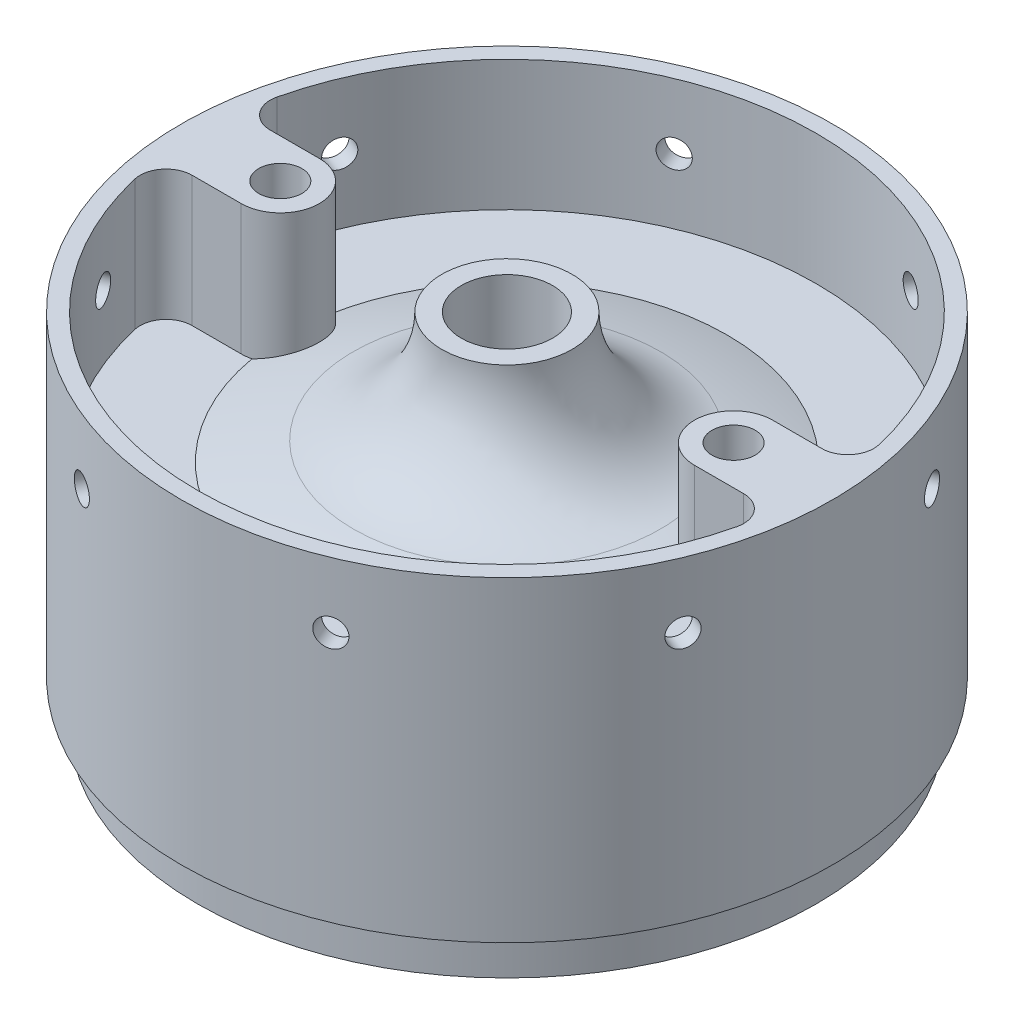
SolidWorks part; units mm, degrees
material "6061-T6 (SS)"
ref_plane "Front Plane" through (0, 0, 0) normal (0, 0, 1) x (1, 0, 0)
ref_plane "Top Plane" through (0, 0, 0) normal (0, 1, 0) x (1, 0, 0)
ref_plane "Right Plane" through (0, 0, 0) normal (1, 0, 0) x (0, 0, -1)
ref_axis "Axis1" through (0, 127.061, 0) along (0, -1, 0)
sketch "Sketch1" plane through (0, 0, 0) normal (0, 0, 1) x (1, 0, 0)
  line L0 (-63.5, 8.1831) -> (-63.5, 69.85)
  line L1 (-60.325, 6.35) -> (-63.5, 8.1831)
  line L2 (0, 127.061) -> (0, -81.9141) construction
  line L3 (-8.9065, 69.85) -> (-12.7, 69.85)
  line L4 (-60.325, 6.35) -> (-60.325, 0)
  line L5 (-60.325, 0) -> (-57.9438, 0)
  line L6 (55, 0) -> (-55, 0) construction
  line L7 (-60.325, 69.85) -> (-63.5, 69.85)
  line L8 (-63.5, 8.1831) -> (-60.325, 6.35)
  line L9 (-60.325, 44.45) -> (-42.968, 44.45)
  line L10 (-8.9065, 69.85) -> (-8.9065, 54.61)
  line L11 (-60.325, 44.45) -> (-60.325, 69.85)
  line L15 (-57.9438, 0) -> (-57.9438, 6.35)
  line L16 (-57.9438, 6.35) -> (-55.5728, 19.7961)
  arc A0 (-55.5728, 19.7961) -> (-42.968, 37.7227) centre (-36.5228, 19.7961) cw
  arc A1 (-42.968, 37.7227) -> (-19.868, 43.6485) centre (0, -81.7878) cw
  arc A2 (-29.9638, 48.1522) -> (-12.7, 69.85) centre (-34.9672, 69.85) ccw
  arc A3 (-42.968, 44.45) -> (-29.9638, 48.1522) centre (0, -81.7878) cw
  arc A4 (-8.9065, 54.61) -> (-19.868, 43.6485) centre (-19.868, 54.61) cw
  point P14 (-59.1344, 0)
  dimension "D5" = 19.05
  dimension "D6" = 127
  dimension "D7" = 133.35
  dimension "D8" = 63.5
  dimension "D12" = 3.175
  dimension "D14" = 15.24
  dimension "D2" = 170
  dimension "D3" = 6.35
  dimension "D4" = 2.3813
  dimension "D9" = 25.4
  dimension "D10" = 3.175
  dimension "D11" = 12.7
  dimension "D13" = 8.9065
  dimension "D16" = 63.5
  dimension "D17" = 120
revolve "Revolve2" add sketch "Sketch1" angle 360 about axis through (0, 127.061, 0) along (0, -1, 0) region at (-43.3861, 40.2185, 0)
sketch "Sketch2" plane through (0, 0, 0) normal (0, 0, 1) x (1, 0, 0)
  line L0 (0, 127.061) -> (0, -81.9141) construction
  line L1 (0, 87.1374) -> (-97.8719, 87.1374)
  line L2 (0, 87.1374) -> (0, -26.2798)
  line L3 (0, -26.2798) -> (-97.8719, -26.2798)
  line L4 (-97.8719, 87.1374) -> (-97.8719, -26.2798)
revolve "Cut-Revolve1" [suppressed] cut sketch "Sketch2" angle 315 about axis through (0, 127.061, 0) along (0, -1, 0)
ref_plane "Plane1" through (0, 57.15, 0) normal (0, 1, 0) x (1, 0, 0)
ref_plane "Plane2" through (0, 0, 0) normal (0.9239, 0, 0.3827) x (0, -1, 0)
ref_axis "Axis2" through (83.9699, 57.15, -202.7212) along (-0.3827, 0, 0.9239)
hole_wizard "#3 (0.213) Diameter Hole1" positions "3DSketch3" profile "Sketch5" hole size "#3" standard "ANSI Inch"
sketch3d "3DSketch3"
  line L0 (83.9699, 57.15, -202.7212) -> (-38.5912, 57.15, 93.1674) construction
  point P0 (-24.3004, 57.15, 58.6664)
sketch "Sketch5" plane through (-24.3004, 57.15, 58.6664) normal (0, 1, 0) x (0.9239, 0, 0.3827)
  line L0 (0, 0) -> (0, 13.3094)
  line L1 (0, 13.3094) -> (2.7051, 11.684)
  line L2 (2.7051, 11.684) -> (2.7051, 0)
  line L5 (2.7051, 0) -> (0, 0)
  line L10 (0, 13.3094) -> (-2.7051, 11.684) construction
  line L11 (0, -6.35) -> (0, 107.95) construction
  dimension "Hole Dia." = 5.4102
  dimension "Hole Depth" = 11.684
  dimension "Drill Angle" = 118
pattern_circular "CirPattern1" count 8 over 360 about axis through (0, 127.061, 0) along (0, -1, 0) of "#3 (0.213) Diameter Hole1"
cosmetic thread "Cosmetic Thread1" parameters "D2"=6.35
hole_wizard "Q (0.332) Diameter Hole2" positions "Sketch9" profile "Sketch10" hole size "Q" standard "ANSI Inch" end condition through all
sketch "Sketch9" plane through (0, 44.45, 0) normal (0, 1, 0) x (1, 0, 0)
  line L0 (-55, 0) -> (55, 0) construction
  circle A1 centre (0, 0) radius 42.968 construction
  point P0 (-44.196, 0)
  dimension "D1" = 44.196
sketch "Sketch10" plane through (-44.196, 44.45, 0) normal (1, 0, 0) x (0, 0, 1)
  line L0 (0, 0) -> (0, 44.45)
  line L1 (0, 44.45) -> (4.2164, 44.45)
  line L2 (4.2164, 44.45) -> (4.2164, 0)
  line L5 (4.2164, 0) -> (0, 0)
  line L11 (0, -6.35) -> (0, 107.95) construction
  dimension "Thru Hole Dia." = 8.4328
  dimension "Thru Hole Depth" = 44.45
sketch "Sketch11" plane through (0, 44.45, 0) normal (0, 1, 0) x (1, 0, 0)
  line L0 (-59.8418, 7.62) -> (-44.196, 7.62)
  line L1 (-59.8418, -7.6199) -> (-44.1961, -7.62)
  circle A0 centre (0, 0) radius 60.325 construction
  arc A2 (-44.196, 7.62) -> (-44.1961, -7.62) centre (-44.196, 0) cw
  circle A3 centre (-44.196, 0) radius 4.2164 construction
  circle A5 centre (0, 0) radius 60.325
  arc A6 (-59.8418, 7.62) -> (-59.8418, -7.6199) centre (0, 0) ccw
  dimension "D1" = 7.62
  dimension "D2" = 7.62
  dimension "D3" = 180
  dimension "D4" = 0
extrude "Boss-Extrude1" add sketch "Sketch11" along normal up to surface (25.4 mm away) up to face at (0, 69.85, 63.5)
fillet "Fillet1" radius 5.08 2 edges at (-59.8418, 57.15, -7.62) (-59.8418, 57.15, 7.6199)
hole_wizard "Q (0.332) Diameter Hole3" positions "Sketch12" profile "Sketch13" hole size "Q" standard "ANSI Inch" end condition up to next
sketch "Sketch12" plane through (0, 44.45, 0) normal (0, -1, 0) x (-1, 0, 0)
  circle A0 centre (44.196, 0) radius 4.2164 construction
  point P0 (44.196, 0)
sketch "Sketch13" plane through (-44.196, 44.45, 0) normal (1, 0, 0) x (0, 0, -1)
  line L0 (0, 0) -> (0, 25.401)
  line L1 (0, 25.401) -> (4.2164, 25.401)
  line L2 (4.2164, 25.401) -> (4.2164, 0)
  line L5 (4.2164, 0) -> (0, 0)
  line L11 (0, -6.35) -> (0, 107.95) construction
  dimension "Thru Hole Dia." = 8.4328
  dimension "Thru Hole Depth" = 25.401
mirror "Mirror1" about plane through (0, 0, 0) normal (1, 0, 0) of "Boss-Extrude1", "Fillet1", "Q (0.332) Diameter Hole3"
